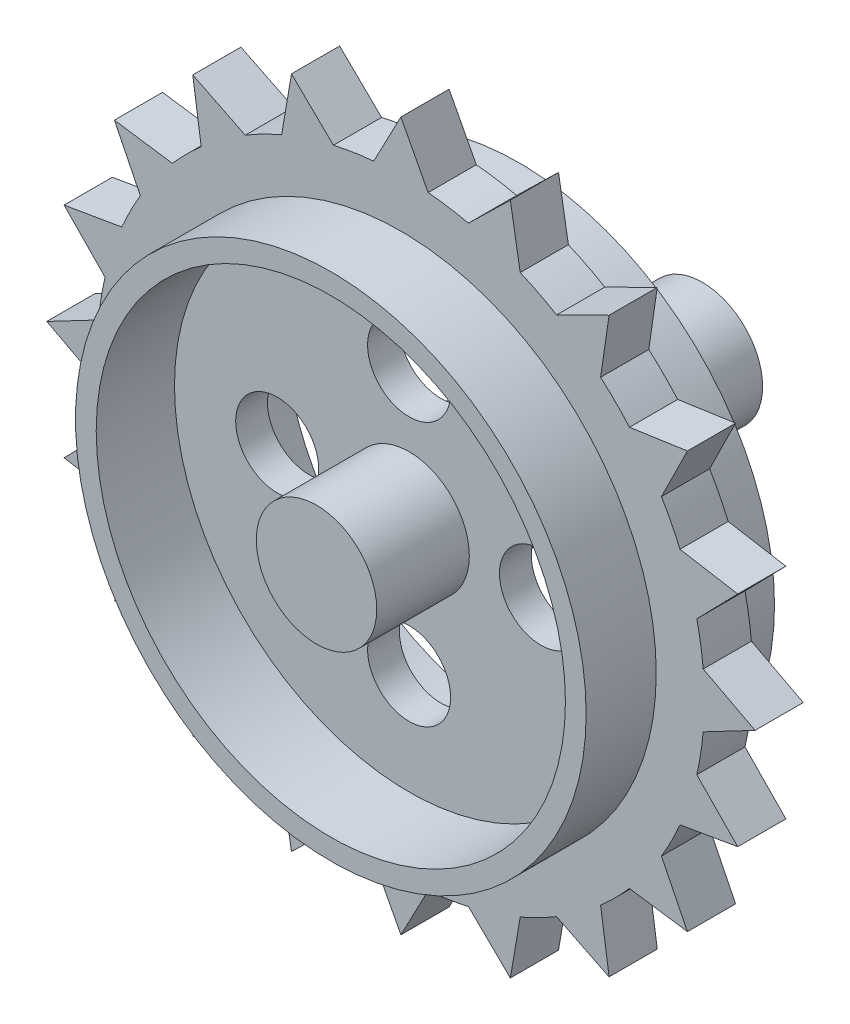
SolidWorks part; units mm, degrees
material "ABS"
ref_plane "Front Plane" through (0, 0, 0) normal (0, 0, 1) x (1, 0, 0)
ref_plane "Top Plane" through (0, 0, 0) normal (0, 1, 0) x (1, 0, 0)
ref_plane "Right Plane" through (0, 0, 0) normal (1, 0, 0) x (0, 0, -1)
sketch "Sketch1" plane through (0, 0, 0) normal (1, 0, 0) x (0, 0, -1)
  line L0 (0, 0) -> (-6.7605, 0) construction
  line L1 (4.9657, 13.462) -> (1.27, 13.462)
  line L2 (-4.9657, 13.462) -> (-4.9657, 12.3698)
  line L3 (4.9657, 13.462) -> (4.9657, 12.3698)
  line L4 (0, 0) -> (0, 16.002) construction
  line L5 (-1.27, 16.002) -> (1.27, 16.002)
  line L6 (-1.27, 16.002) -> (-1.27, 13.462)
  line L7 (1.27, 16.002) -> (1.27, 13.462)
  line L8 (-1.27, 13.462) -> (-4.9657, 13.462)
  line L9 (-4.9657, 12.3698) -> (-0.8382, 12.3698)
  line L10 (4.9657, 12.3698) -> (0.8382, 12.3698)
  line L11 (-0.8382, 12.3698) -> (-0.8382, 3.175)
  line L12 (-0.8382, 3.175) -> (-5.7198, 3.175)
  line L13 (-5.7198, 3.175) -> (-5.7198, 0)
  line L14 (-5.7198, 0) -> (0, 0)
  line L15 (0, 0) -> (14.6256, 0)
  line L16 (14.6256, 0) -> (14.6256, 3.175)
  line L17 (14.6256, 3.175) -> (0.8382, 3.175)
  line L18 (0.8382, 3.175) -> (0.8382, 12.3698)
  dimension "D1" = 26.924
  dimension "D2" = 1.0922
  dimension "D3" = 9.9314
  dimension "D4" = 32.004
  dimension "D5" = 2.54
  dimension "D6" = 4.1275
  dimension "D7" = 4.8816
  dimension "D8" = 6.35
  dimension "D9" = 20.3454
revolve "Revolve1" add sketch "Sketch1" angle 360 about L15
sketch "Sketch3" plane through (0, 0, -14.6256) normal (0, 0, -1) x (-1, 0, 0)
  line L1 (1.5398, 0) -> (0.7699, 1.3335)
  line L2 (0.7699, 1.3335) -> (-0.7699, 1.3335)
  line L3 (-0.7699, 1.3335) -> (-1.5398, 0)
  line L4 (-1.5398, 0) -> (-0.7699, -1.3335)
  line L5 (-0.7699, -1.3335) -> (0.7699, -1.3335)
  line L6 (0.7699, -1.3335) -> (1.5398, 0)
  circle A0 centre (0, 0) radius 1.3335 construction
  dimension "D1" = 2.667
extrude "Cut-Extrude2" cut sketch "Sketch3" against normal blind 17.78
sketch "Sketch4" plane through (0, 0, -0.8382) normal (0, 0, -1) x (-1, 0, 0)
  line L0 (0, 13.462) -> (0, 0) construction
  circle A0 centre (0, 6.9546) radius 2.1894
  circle A1 centre (6.9546, 0) radius 2.1894
  circle A2 centre (0, -6.9546) radius 2.1894
  circle A3 centre (-6.9546, 0) radius 2.1894
  circle A4 centre (0, 0) radius 13.462 construction
  circle A5 centre (0, 0) radius 13.462 construction
  point P12 (0, 0)
  point P17 (10.3507, -1.8529)
  point P18 (0, 0)
  point P19 (0, 10.6021)
  dimension "D2" = 4.3789
  dimension "D3" = 4.318
  dimension "D1" = 4
extrude "Cut-Extrude3" cut sketch "Sketch4" against normal up to surface (1.6764 mm away) up to face at (3.175, 0, 0.8382)
sketch "Sketch5" plane through (0, 0, 1.27) normal (0, 0, 1) x (1, 0, 0)
  line L0 (0, 0) -> (18.6715, 0) construction
  line L1 (18.6715, 0) -> (15.9375, 1.4351)
  line L2 (18.6715, 0) -> (15.9375, -1.4351)
  line L3 (17.7576, -5.7698) -> (14.714, -6.2898)
  line L4 (17.7576, -5.7698) -> (15.601, -3.5601)
  line L5 (15.1055, -10.9748) -> (12.0502, -10.5289)
  line L6 (15.1055, -10.9748) -> (13.7373, -8.2068)
  line L7 (10.9748, -15.1055) -> (8.2068, -13.7373)
  line L8 (10.9748, -15.1055) -> (10.5289, -12.0502)
  line L9 (5.7698, -17.7576) -> (3.5601, -15.601)
  line L10 (5.7698, -17.7576) -> (6.2898, -14.714)
  line L11 (0, -18.6715) -> (-1.4351, -15.9375)
  line L12 (0, -18.6715) -> (1.4351, -15.9375)
  line L13 (-5.7698, -17.7576) -> (-6.2898, -14.714)
  line L14 (-5.7698, -17.7576) -> (-3.5601, -15.601)
  line L15 (-10.9748, -15.1055) -> (-10.5289, -12.0502)
  line L16 (-10.9748, -15.1055) -> (-8.2068, -13.7373)
  line L17 (-15.1055, -10.9748) -> (-13.7373, -8.2068)
  line L18 (-15.1055, -10.9748) -> (-12.0502, -10.5289)
  line L19 (-17.7576, -5.7698) -> (-15.601, -3.5601)
  line L20 (-17.7576, -5.7698) -> (-14.714, -6.2898)
  line L21 (-18.6715, 0) -> (-15.9375, 1.4351)
  line L22 (-18.6715, 0) -> (-15.9375, -1.4351)
  line L23 (-17.7576, 5.7698) -> (-14.714, 6.2898)
  line L24 (-17.7576, 5.7698) -> (-15.601, 3.5601)
  line L25 (-15.1055, 10.9748) -> (-12.0502, 10.5289)
  line L26 (-15.1055, 10.9748) -> (-13.7373, 8.2068)
  line L27 (-10.9748, 15.1055) -> (-8.2068, 13.7373)
  line L28 (-10.9748, 15.1055) -> (-10.5289, 12.0502)
  line L29 (-5.7698, 17.7576) -> (-3.5601, 15.601)
  line L30 (-5.7698, 17.7576) -> (-6.2898, 14.714)
  line L31 (0, 18.6715) -> (1.4351, 15.9375)
  line L32 (0, 18.6715) -> (-1.4351, 15.9375)
  line L33 (5.7698, 17.7576) -> (6.2898, 14.714)
  line L34 (5.7698, 17.7576) -> (3.5601, 15.601)
  line L35 (10.9748, 15.1055) -> (10.5289, 12.0502)
  line L36 (10.9748, 15.1055) -> (8.2068, 13.7373)
  line L37 (15.1055, 10.9748) -> (13.7373, 8.2068)
  line L38 (15.1055, 10.9748) -> (12.0502, 10.5289)
  line L39 (17.7576, 5.7698) -> (15.601, 3.5601)
  line L40 (17.7576, 5.7698) -> (14.714, 6.2898)
  circle A0 centre (0, 0) radius 16.002 construction
  circle A1 centre (0, 0) radius 16.002
  point P3 (16.002, 0)
  point P67 (0, 0)
  circle M44 centre (0, 0) radius 16.002
  dimension "D1" = 2.8702
  dimension "D2" = 2.6695
  dimension "D3" = 20
extrude "Boss-Extrude1" add sketch "Sketch5" against normal up to surface (2.54 mm away) contours L25 L26 M44 | L27 L28 M44 | L29 L30 M44 | L31 L32 M44 | L33 L34 M44 | L35 L36 M44 | L37 L38 M44 | L39 L40 M44 | L0 L2 M44 | A1 L0 L1 | L3 L4 M44 | L5 L6 M44 | L7 L8 M44 | L9 L10 M44 | L11 L12 M44 | L13 L14 M44 | L15 L16 M44 | L17 L18 M44 | L19 L20 M44 | L21 L22 M44 | L23 L24 M44 region at (16.8776, 0.4764, 1.27) region at (16.8776, -0.4764, 1.27) region at (16.0515, 5.2155, 1.27) region at (16.0515, -5.2155, 1.27) region at (13.6543, 9.9204, 1.27) region at (13.6543, -9.9204, 1.27) region at (9.9204, 13.6543, 1.27) region at (9.9204, -13.6543, 1.27) region at (5.2155, 16.0515, 1.27) region at (5.2155, -16.0515, 1.27) region at (0, 16.8776, 1.27) region at (0, -16.8776, 1.27) region at (-5.2155, 16.0515, 1.27) region at (-5.2155, -16.0515, 1.27) region at (-9.9204, 13.6543, 1.27) region at (-9.9204, -13.6543, 1.27) region at (-13.6543, 9.9204, 1.27) region at (-13.6543, -9.9204, 1.27) region at (-16.0515, 5.2155, 1.27) region at (-16.0515, -5.2155, 1.27) region at (-16.8776, 0, 1.27) up to face at (16.002, 0, -1.27)
